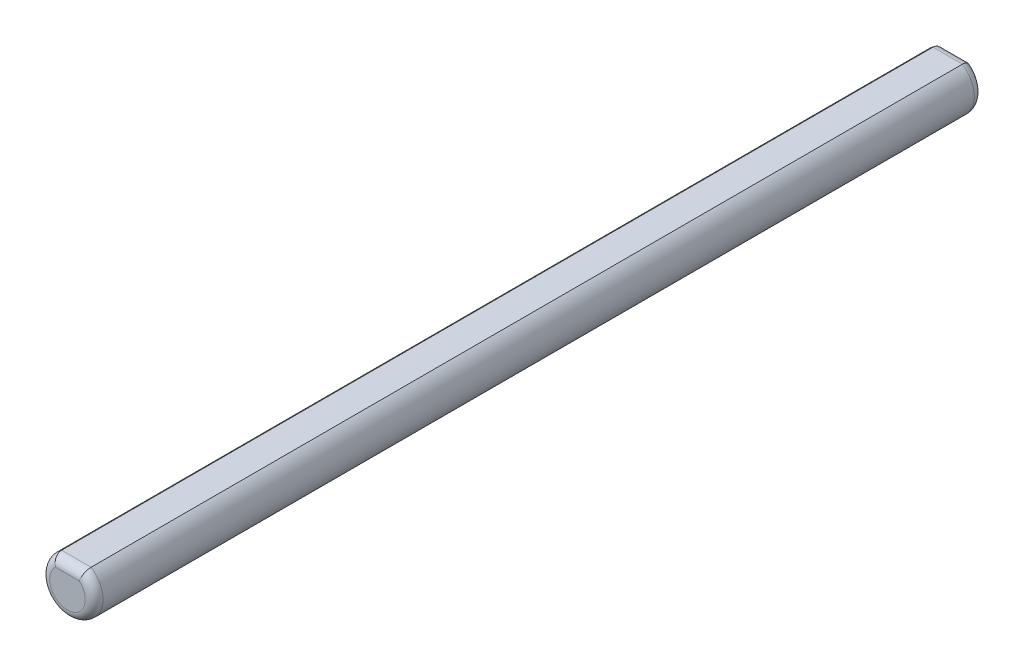
SolidWorks part; units mm, degrees
ref_plane "Front Plane" through (0, 0, 0) normal (0, 0, 1) x (1, 0, 0)
ref_plane "Top Plane" through (0, 0, 0) normal (0, 1, 0) x (1, 0, 0)
ref_plane "Right Plane" through (0, 0, 0) normal (1, 0, 0) x (0, 0, -1)
ref_plane "Plane1" through (0, 0, 115.1204) normal (0, 0, 1) x (1, 0, 0)
sketch "Sketch1" plane through (0, 0, 115.1204) normal (0, 0, 1) x (1, 0, 0)
  line L0 (43.606, 44.3643) -> (40.2894, 44.3643)
  arc A0 (40.2894, 44.3643) -> (43.606, 44.3643) centre (41.9477, 41.8643) ccw
extrude "Boss-Extrude1" add sketch "Sketch1" against normal blind 100
fillet "Fillet1" radius 1 4 edges at (41.9477, 44.3643, 15.1204) (41.9477, 38.8643, 15.1204) (41.9477, 44.3643, 115.1204) (41.9477, 38.8643, 115.1204)
